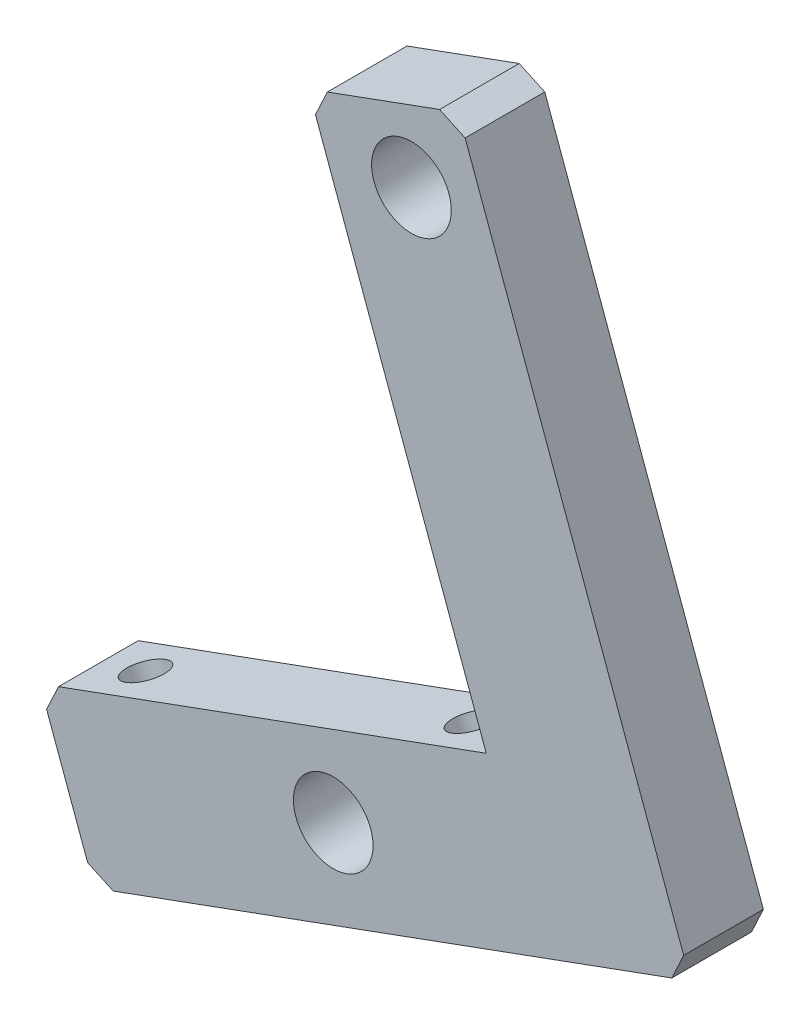
SolidWorks part; units mm, degrees
ref_plane "前基準面" through (0, 0, 0) normal (0, 0, 1) x (1, 0, 0)
ref_plane "上基準面" through (0, 0, 0) normal (0, 1, 0) x (1, 0, 0)
ref_plane "右基準面" through (0, 0, 0) normal (1, 0, 0) x (0, 0, -1)
sketch "草圖1" plane through (0, 0, 0) normal (0, 0, 1) x (1, 0, 0)
  line L0 (-29.9561, 9.7552) -> (-48.7426, 2.8947)
  line L1 (24.4386, -12.4483) -> (-40.3701, 14.0061) construction
  line L2 (-48.7426, 2.8947) -> (-26.446, -58.1615)
  line L3 (-26.446, -58.1615) -> (-82.4902, -78.6278)
  line L4 (-82.4902, -78.6278) -> (-75.6297, -97.4144)
  line L5 (-75.6297, -97.4144) -> (-0.799, -70.0876)
  line L6 (-0.799, -70.0876) -> (-29.9561, 9.7552)
  circle A0 centre (-35.8357, -1.3461) radius 5
  circle A1 centre (-45.6546, -75.3171) radius 5
  dimension "D4" = 10
  dimension "D5" = 10
  dimension "D1" = 20
  dimension "D2" = 20
  dimension "D3" = 65
extrude "填料-伸長1" add sketch "草圖1" along normal blind 10
sketch "草圖2" plane through (15.6286, -42.7967, 0) normal (-0.343, 0.9393, 0) x (0.9393, 0.343, 0)
  circle A0 centre (-95.6715, -4.9822) radius 2.5
  circle A1 centre (-52.1263, -4.9822) radius 2.5
  dimension "D1" = 5
  dimension "D2" = 5
extrude "除料-伸長2" cut sketch "草圖2" against normal through all
chamfer "導角1" distance 2.5 angle 45 5 edges at (-29.9561, 9.7552, 5) (-48.7426, 2.8947, 5) (-0.799, -70.0876, 5) (-75.6297, -97.4144, 5) (-82.4902, -78.6278, 5)
